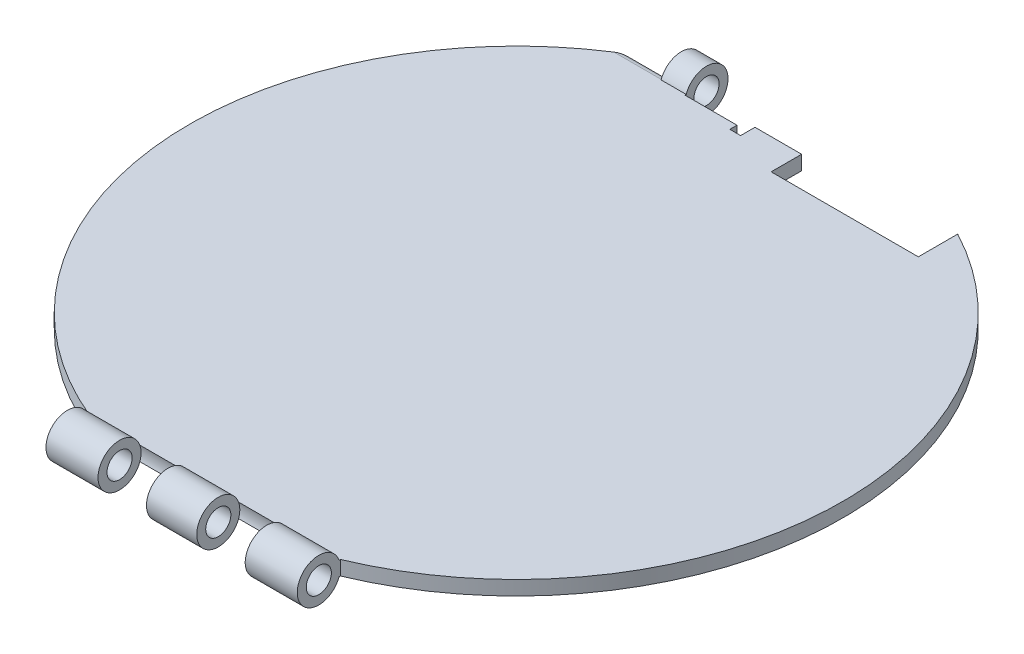
SolidWorks part; units mm, degrees
ref_plane "Front Plane" through (0, 0, 0) normal (0, 0, 1) x (1, 0, 0)
ref_plane "Top Plane" through (0, 0, 0) normal (0, 1, 0) x (1, 0, 0)
ref_plane "Right Plane" through (0, 0, 0) normal (1, 0, 0) x (0, 0, -1)
sketch "Sketch1" plane through (0, 0, 0) normal (0, 1, 0) x (1, 0, 0)
  line L0 (-17.5, -42) -> (17.5, -42)
  line L1 (0, 0) -> (36.3754, 0) construction
  line L2 (-17.5, 42) -> (17.5, 42)
  arc A0 (-17.5, 42) -> (-17.5, -42) centre (0, 0) ccw
  arc A1 (17.5, -42) -> (17.5, 42) centre (0, 0) ccw
  dimension "D1" = 91
  dimension "D2" = 42
  dimension "D3" = 42
extrude "Boss-Extrude1" add sketch "Sketch1" along normal blind 2
sketch "Sketch2" plane through (0, 0, 0) normal (1, 0, 0) x (0, 0, -1)
  line L0 (-43.0566, 1) -> (50.2125, 1) construction
  line L1 (-42, 2) -> (-42, 0) construction
  line L2 (-42, 0) -> (-42.1716, 0)
  line L3 (-42, 0) -> (42, 0) construction
  line L4 (-42, 0) -> (-42, 1)
  line L5 (-42, 1) -> (-42, 2)
  line L6 (-42, 2) -> (-42.1716, 2)
  line L7 (42, 2) -> (-42, 2) construction
  circle A0 centre (-45, 1) radius 1.75
  arc A1 (-42.1716, 2) -> (-42.1716, 0) centre (-45, 1) ccw
  point P4 (-42, 1)
  dimension "D1" = 6
  dimension "D2" = 3.5
extrude "Boss-Extrude2" add sketch "Sketch2" along normal up to vertex (17.5 mm away) and the other way up to vertex (17.5 mm away) up to point (17.5, 2, 42) other way up to point (-17.5, 2, 42)
ref_plane "Plane1" through (3.5, 0, 0) normal (1, 0, 0) x (0, 0, -1)
sketch "Sketch3" plane through (3.5, 0, 0) normal (1, 0, 0) x (0, 0, -1)
  circle A0 centre (-45, 1) radius 3
  arc A1 (-42.1716, 2) -> (-42.1716, 0) centre (-45, 1) ccw construction
extrude "Cut-Extrude1" cut sketch "Sketch3" along normal blind 6.75
mirror "Mirror1" about plane through (0, 0, 0) normal (1, 0, 0) of "Cut-Extrude1"
sketch "Sketch4" plane through (0, 2, 0) normal (0, 1, 0) x (1, 0, 0)
  line L0 (17.5, 42) -> (-17.5, 42) construction
  line L1 (0.75, 42) -> (21.25, 42)
  line L2 (0.75, 38) -> (0.75, 34.75)
  line L3 (0.75, 34.75) -> (21.25, 34.75)
  line L4 (21.25, 42) -> (21.25, 34.75)
  line L6 (0.75, 42) -> (-17.5, 42)
  line L8 (-7.25, 38) -> (-17.5, 38)
  line L9 (-17.5, 42) -> (-17.5, 38)
  line L11 (0.75, 38) -> (0.75, 39)
  line L12 (0.75, 39) -> (-5.75, 39)
  line L13 (-5.75, 38) -> (-5.75, 39)
  line L15 (-5.75, 38) -> (-5.75, 37)
  line L16 (-5.75, 37) -> (-7.25, 37)
  line L17 (-7.25, 38) -> (-7.25, 37)
  point P6 (17.5, 42)
  point P18 (0, 0)
  point P19 (0.75, 36.4582)
  point P20 (0, 0)
  dimension "D1" = 7.25
  dimension "D2" = 16.75
  dimension "D3" = 3.75
  dimension "D4" = 4
  dimension "D5" = 18.25
  dimension "D6" = 6.5
  dimension "D7" = 1
  dimension "D8" = 1.5
  dimension "D9" = 1
extrude "Cut-Extrude2" cut sketch "Sketch4" against normal up to surface (2 mm away) up to face at (0, 0, 25.3029)
sketch "Sketch5" plane through (-17.5, 0, 0) normal (1, 0, 0) x (0, 0, -1)
  line L0 (36.24, 1) -> (48.3245, 1) construction
  line L1 (38, 0) -> (42, 0) construction
  line L2 (42, 2) -> (38, 2) construction
  line L3 (41, 2.8351) -> (41, -0.8726) construction
  line L4 (42, 2) -> (42, 0) construction
  line L5 (38, 1) -> (38, 2)
  line L6 (38, 2) -> (38.1716, 2)
  line L7 (38, 1) -> (38, 0)
  line L8 (38, 0) -> (38.1716, 0)
  line L10 (38, 0) -> (38, 2) construction
  arc A0 (38.1716, 0) -> (38.1716, 2) centre (41, 1) ccw
  point P7 (38.1716, 0)
  point P21 (0, 0)
  point P25 (38.098, 2)
  dimension "D1" = 6
  dimension "D2" = 1
extrude "Boss-Extrude4" add sketch "Sketch5" along normal blind 3 and the other way blind 0.5
sketch "Sketch6" plane through (-14.5, 0, 0) normal (1, 0, 0) x (0, 0, -1)
  circle A0 centre (41, 1) radius 1.75
  arc A1 (38.1716, 0) -> (38.1716, 2) centre (41, 1) ccw construction
  dimension "D1" = 3.5
extrude "Cut-Extrude3" cut sketch "Sketch6" against normal through all
fillet "Fillet1" radius 1 2 edges at (-20.2356, 0, -39.5639) (-20.2356, 2, -39.5639)
